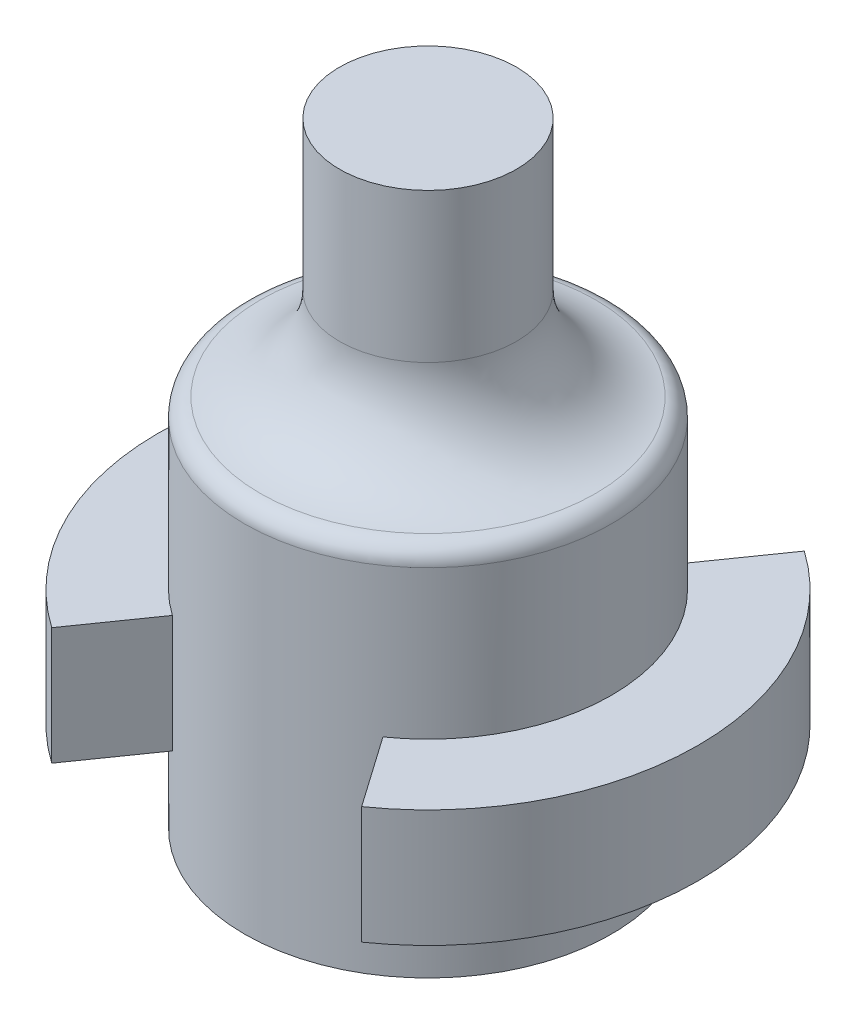
SolidWorks part; units mm, degrees
ref_plane "Alzado" through (0, 0, 0) normal (0, 0, 1) x (1, 0, 0)
ref_plane "Planta" through (0, 0, 0) normal (0, 1, 0) x (1, 0, 0)
ref_plane "Vista lateral" through (0, 0, 0) normal (1, 0, 0) x (0, 0, -1)
sketch "Croquis1" plane through (0, 0, 0) normal (0, 1, 0) x (1, 0, 0)
  line L0 (0, 4.925) -> (0, -4.925) construction
  line L1 (0, 0) -> (-2.8249, 4.0343) construction
  line L2 (0, 0) -> (-2.8249, -4.0343) construction
  line L3 (0, 0) -> (2.8249, -4.0343) construction
  line L4 (0, 0) -> (2.8249, 4.0343) construction
  line L5 (2.8249, 4.0343) -> (4.1584, 5.9389)
  line L6 (-2.8249, 4.0343) -> (-4.1584, 5.9389)
  line L7 (-2.8249, -4.0343) -> (-4.1584, -5.9389)
  line L8 (2.8249, -4.0343) -> (4.1584, -5.9389)
  circle A0 centre (0, 0) radius 4.925
  arc A1 (-4.1584, 5.9389) -> (-4.1584, -5.9389) centre (0, 0) ccw
  arc A2 (4.1584, -5.9389) -> (4.1584, 5.9389) centre (0, 0) ccw
  dimension "D3" = 14.5
  dimension "D4" = 9.85
  dimension "D1" = 35
  dimension "D2" = 35
extrude "Saliente-Extruir1" add sketch "Croquis1" along normal blind 3.15 from offset 0.4 contours L6 A1 L7 A0 | L8 A2 L5 A0 region at (5.2579, 0, 0) region at (-5.2579, 0, 0)
extrude "Saliente-Extruir2" add sketch "Croquis1<3>" along normal blind 8 contours A0 region at (0, 0, 0)
sketch "Croquis1<3>" plane through (0, 0, 0) normal (0, 1, 0) x (1, 0, 0) same geometry as "Croquis1"
extrude "Saliente-Extruir3" add sketch "Croquis1<4>" against normal blind 2 contours A0 region at (0, 0, 0)
sketch "Croquis1<4>" plane through (0, 0, 0) normal (0, 1, 0) x (1, 0, 0) same geometry as "Croquis1"
sketch "Croquis2" plane through (0, 8, 0) normal (0, 1, 0) x (1, 0, 0)
  circle A0 centre (0, 0) radius 2.375
  dimension "D1" = 4.75
extrude "Saliente-Extruir4" add sketch "Croquis2" along normal blind 6.5
fillet "Redondeo2" radius 2.5 1 edges at (0, 8, 2.375)
fillet "Redondeo3" radius 0.5 1 edges at (0, 8, 4.925)
